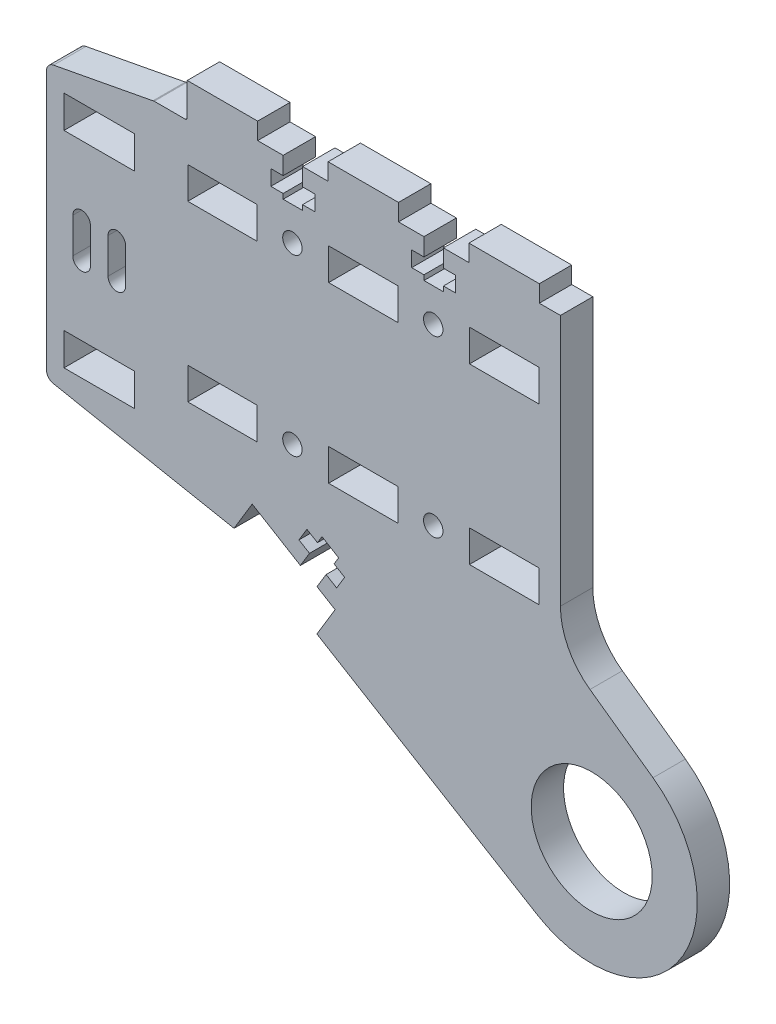
SolidWorks part; units mm, degrees
ref_plane "Front Plane" through (0, 0, 0) normal (0, 0, 1) x (1, 0, 0)
ref_plane "Top Plane" through (0, 0, 0) normal (0, 1, 0) x (1, 0, 0)
ref_plane "Right Plane" through (0, 0, 0) normal (1, 0, 0) x (0, 0, -1)
sketch "Sketch1" plane through (0, 0, 0) normal (0, 0, 1) x (1, 0, 0)
  line L0 (-38.0203, 0) -> (38.1796, 0) construction
  line L1 (31.7297, -12.8) -> (19.2297, -12.8)
  line L2 (38.1796, -12.8536) -> (38.1796, 12.8536)
  line L3 (31.7297, 12.8) -> (19.2297, 12.8)
  line L4 (-38.0203, -12.8) -> (-38.0203, 12.8)
  line L5 (38.1796, -12.8536) -> (-38.0203, 12.8) construction
  line L6 (38.1796, 12.8536) -> (-38.0203, -12.8) construction
  line L7 (6.3297, 18.542) -> (-6.1703, 18.542)
  line L8 (-19.0703, -18.542) -> (-31.5703, -12.8) construction
  line L9 (-19.0703, -12.8) -> (-31.5703, -18.542) construction
  line L10 (6.3297, -12.8) -> (-6.1703, -12.8)
  line L11 (-19.0703, -12.8) -> (-31.5703, -12.8)
  line L12 (31.7297, -12.8) -> (31.7297, -18.542)
  line L13 (19.2297, -12.8) -> (19.2297, -18.542)
  line L14 (38.1796, 28.575) -> (31.8297, 28.575)
  line L15 (-19.0703, 12.8) -> (-19.0703, 18.542)
  line L16 (-19.0703, 18.542) -> (-31.5703, 18.542)
  line L17 (-31.5703, 12.8) -> (-31.5703, 18.542)
  line L18 (-19.0703, 12.8) -> (-31.5703, 18.542) construction
  line L19 (-19.0703, 18.542) -> (-31.5703, 12.8) construction
  line L20 (-6.1703, 12.8) -> (-6.1703, 18.542)
  line L21 (6.3297, 12.8) -> (6.3297, 18.542)
  line L22 (31.7297, 18.542) -> (19.2297, 18.542)
  line L23 (19.2297, 12.8) -> (19.2297, 18.542)
  line L24 (31.7297, 12.8) -> (31.7297, 18.542)
  line L25 (-19.0703, 12.8) -> (-31.5703, 12.8)
  line L26 (6.3297, 12.8) -> (-6.1703, 12.8)
  line L27 (-38.0203, 12.8) -> (-38.0203, 28.575)
  line L28 (0.0797, 0) -> (0.0797, 28.575) construction
  line L29 (11.0271, 28.575) -> (6.4297, 28.575)
  line L30 (38.1796, 28.575) -> (38.1796, 12.8536)
  line L31 (31.7297, -18.542) -> (19.2297, -18.542)
  line L32 (6.3297, -12.8) -> (6.3297, -18.542)
  line L33 (-6.1703, -12.8) -> (-6.1703, -18.542)
  line L34 (-31.5703, -12.8) -> (-31.5703, -18.542)
  line L35 (-19.0703, -18.542) -> (-31.5703, -18.542)
  line L36 (-19.0703, -12.8) -> (-19.0703, -18.542)
  line L37 (6.3297, -18.542) -> (-6.1703, -18.542)
  line L38 (31.7297, -12.8) -> (19.2297, -12.8)
  line L39 (-19.0703, -12.8) -> (-31.5703, -12.8)
  line L40 (6.3297, -12.8) -> (-6.1703, -12.8)
  line L41 (6.3297, 12.8) -> (19.2297, 12.8) construction
  line L42 (-38.0203, -25.196) -> (31.432, -67.11)
  line L43 (38.1796, -25.196) -> (52.3348, -35.2893)
  line L44 (-10.8677, 22.1694) -> (-14.3729, 22.1694) construction
  line L45 (-8.6516, 24.0109) -> (-16.5891, 24.0109) construction
  line L46 (-10.8677, 26.9875) -> (-14.3729, 26.9875) construction
  line L47 (-12.6203, 28.575) -> (-12.6203, 24.5335) construction
  line L48 (-6.1703, 12.8) -> (-19.0703, 12.8) construction
  line L49 (-14.3729, 21.717) -> (-14.3729, 22.6219)
  line L50 (12.7797, 0) -> (12.7797, 28.575) construction
  line L51 (14.5323, 25.4) -> (16.7484, 25.4)
  line L52 (14.5323, 22.6219) -> (16.7484, 22.6219)
  line L53 (11.0271, 25.4) -> (11.0271, 28.575)
  line L54 (-10.8677, 21.717) -> (-10.8677, 22.6219)
  line L55 (-38.0203, -12.8) -> (-38.0203, -25.196)
  line L56 (14.5323, 25.4) -> (14.5323, 28.575)
  line L57 (12.7797, 28.575) -> (12.7797, 24.5335) construction
  line L58 (38.1796, -12.8536) -> (38.1796, -25.196)
  line L59 (11.0271, 26.9875) -> (14.5323, 26.9875) construction
  line L60 (8.8109, 22.6219) -> (11.0271, 22.6219)
  line L61 (8.8109, 22.6219) -> (8.8109, 25.4)
  line L62 (8.8109, 25.4) -> (11.0271, 25.4)
  line L63 (16.7484, 22.6219) -> (16.7484, 25.4)
  line L64 (12.7797, 24.5335) -> (12.7797, 20.1202) construction
  line L65 (8.8109, 24.0109) -> (16.7484, 24.0109) construction
  line L66 (11.0271, 21.717) -> (14.5323, 21.717)
  line L67 (11.0271, 21.717) -> (11.0271, 22.6219)
  line L68 (-6.2703, 28.575) -> (-10.8677, 28.575)
  line L69 (14.5323, 21.717) -> (14.5323, 22.6219)
  line L70 (12.7797, 20.1202) -> (12.7797, 21.717) construction
  line L71 (11.0271, 22.1694) -> (14.5323, 22.1694) construction
  line L72 (-10.8677, 21.717) -> (-14.3729, 21.717)
  line L73 (-16.5891, 22.6219) -> (-16.5891, 25.4)
  line L74 (-8.6516, 25.4) -> (-10.8677, 25.4)
  line L75 (-8.6516, 22.6219) -> (-8.6516, 25.4)
  line L76 (-8.6516, 22.6219) -> (-10.8677, 22.6219)
  line L77 (-14.3729, 25.4) -> (-14.3729, 28.575)
  line L78 (-10.8677, 25.4) -> (-10.8677, 28.575)
  line L79 (-14.3729, 22.6219) -> (-16.5891, 22.6219)
  line L80 (-14.3729, 25.4) -> (-16.5891, 25.4)
  line L81 (-14.3729, 28.575) -> (-18.9703, 28.575)
  line L82 (19.1297, 31.623) -> (19.1297, 28.575)
  line L83 (-6.2703, 31.623) -> (6.4297, 31.623)
  line L84 (-6.2703, 31.623) -> (-6.2703, 28.575)
  line L85 (31.8297, 31.623) -> (31.8297, 28.575)
  line L86 (6.4297, 31.623) -> (6.4297, 28.575)
  line L87 (0.0797, 28.575) -> (0.0797, 31.623) construction
  line L88 (-6.2703, 30.099) -> (6.4297, 30.099) construction
  line L89 (31.8297, 30.099) -> (19.1297, 30.099) construction
  line L90 (31.8297, 31.623) -> (19.1297, 31.623)
  line L91 (19.1297, 28.575) -> (14.5323, 28.575)
  line L92 (-18.9703, 31.623) -> (-18.9703, 28.575)
  line L93 (-31.6703, 31.623) -> (-18.9703, 31.623)
  line L94 (-31.6703, 30.099) -> (-18.9703, 30.099) construction
  line L95 (-31.6703, 31.623) -> (-31.6703, 28.575)
  line L96 (-31.6703, 28.575) -> (-38.0203, 28.575)
  arc A0 (31.432, -67.11) -> (52.3348, -35.2893) centre (41.275, -50.8) ccw
  circle A1 centre (12.7, 15.721) radius 1.7526
  circle A2 centre (-12.7, 15.721) radius 1.7526
  circle A3 centre (12.7, -15.721) radius 1.7526
  circle A4 centre (-12.7, -15.721) radius 1.7526
  circle A6 centre (41.275, -50.8) radius 10.9125
  point P0 (0, 0)
  point P8 (-25.3203, 15.671)
  point P16 (12.7, 30.1625)
  point P37 (-25.3203, -15.671)
  point P55 (12.7797, 26.9875)
  point P59 (12.7797, 24.0109)
  point P60 (-0.4211, 99.3522)
  point P62 (-25.6211, 23.1522)
  point P65 (12.7797, 22.1694)
  point P70 (-3.225, -28.575)
  point P73 (12.7797, 24.0109)
  point P91 (-12.6203, 24.0109)
  point P92 (-12.6203, 22.1694)
  point P97 (-12.6203, 26.9875)
  point P98 (-12.5407, 30.1625)
  point P99 (0.0797, 30.099)
  point P117 (25.4797, 30.099)
  point P120 (-25.3203, 30.099)
  dimension "D3" = 12.5
  dimension "D5" = 50.8
  dimension "D6" = 41.275
  dimension "D8" = 12.7
  dimension "D13" = 3.5052
  dimension "D11" = 28.575
  dimension "D19" = 21.825
  dimension "D7" = 38.1
  dimension "D1" = 25.6
  dimension "D2" = 76.2
  dimension "D4" = 5.742
  dimension "D9" = 12.7
  dimension "D10" = 3
  dimension "D12" = 2.921
  dimension "D14" = 2.921
  dimension "D15" = 15.721
  dimension "D16" = 12.7
  dimension "D17" = 3.048
  dimension "D20" = 9.525
  dimension "D21" = 9.525
  dimension "D18" = 12.7
  dimension "D22" = 3.5052
  dimension "D23" = 2.7781
  dimension "D24" = 7.9375
  dimension "D25" = 3.175
  dimension "D26" = 0.9049
extrude "Boss-Extrude1" add sketch "Sketch1" along normal blind 5.842 contours L58 L2 L30 L27 L4 L55 A4 L32 L37 L33 L10 L11 L36 L35 L34 L12 L31 L13 L1 L21 L26 L20 L7 L15 L25 L17 L16 L24 L3 L23 L22 region at (7.1681, -13.709, 0)
fillet "Fillet1" [suppressed] radius 3.175
fillet "Fillet2" [suppressed] radius 3.175
fillet "Fillet3" [suppressed] radius 3.175
sketch "Sketch3" [suppressed] plane through (0, 0, 5.842) normal (0, 0, 1) x (1, 0, 0)
  line L0 (12.6, 94.996) -> (12.7, -15.721) construction
  circle A0 centre (12.7147, -32.004) radius 2.413
  dimension "D1" = 4.826
  dimension "D2" = 127
extrude "Cut-Extrude2" [suppressed] cut sketch "Sketch3" against normal through all
sketch "Sketch5" [suppressed] plane through (0, 0, 5.842) normal (0, 0, 1) x (1, 0, 0)
  line L1 (-55.0734, 111.0269) -> (34.825, 111.0269)
  line L2 (-55.0734, 111.0269) -> (-55.0734, 25.146)
  line L3 (-55.0734, 25.146) -> (34.825, 25.146)
  line L4 (34.825, 111.0269) -> (34.825, 25.146)
extrude "Cut-Extrude3" [suppressed] cut sketch "Sketch5" against normal through all
sketch "Sketch6" [suppressed] plane through (0, 0, 5.842) normal (0, 0, 1) x (1, 0, 0)
  line L0 (-34.925, 25.146) -> (-33.9441, 25.146) construction
  line L1 (31.4879, 25.146) -> (-22.4871, 25.146)
  line L2 (31.4879, 78.486) -> (34.6629, 74.676)
  line L3 (31.4879, 78.486) -> (-20.5821, 78.486)
  line L4 (-22.4871, 25.146) -> (-25.0279, 25.146)
  line L5 (34.6629, 25.146) -> (-22.4871, 78.486) construction
  line L6 (34.6629, 78.486) -> (-22.4871, 25.146) construction
  line L7 (6.0879, 25.146) -> (6.0879, 48.411) construction
  line L8 (-31.75, 25.146) -> (-22.4871, 51.816)
  line L9 (-38.1, -25.146) -> (-38.1, 25.4) construction
  line L10 (34.6629, 74.676) -> (34.6629, 41.021)
  line L11 (-31.75, 25.146) -> (-25.0279, 25.146)
  line L12 (-22.4871, 51.816) -> (-22.4871, 71.3764)
  line L13 (31.4879, 70.866) -> (31.4879, 42.926) construction
  line L14 (31.4879, 37.846) -> (31.4879, 25.146)
  line L15 (31.4879, 37.846) -> (34.6629, 41.021)
  circle A0 centre (31.4879, 70.866) radius 1.651
  circle A1 centre (31.4879, 42.926) radius 1.651
  circle A2 centre (-20.5821, 74.676) radius 1.651
  circle A3 centre (-19.3121, 27.686) radius 1.651
  arc A4 (-20.5821, 78.486) -> (-22.4871, 71.3764) centre (-20.5821, 74.676) ccw
  point P0 (6.0879, 51.816)
  point P13 (-25.7515, 23.0626)
  point P14 (-16.4886, 49.7326)
  dimension "D5" = 3.302
  dimension "D6" = 3.302
  dimension "D9" = 12.7
  dimension "D10" = 3.302
  dimension "D12" = 3.302
  dimension "D1" = 53.34
  dimension "D2" = 57.15
  dimension "D3" = 6.35
  dimension "D7" = 49.53
  dimension "D8" = 27.94
  dimension "D11" = 52.07
  dimension "D13" = 50.8
  dimension "D14" = 15.24
  dimension "D4" = 7.62
extrude "Boss-Extrude3" [suppressed] add sketch "Sketch6" against normal up to surface (5.842 mm away) up to face at (52.1875, -50.8, 0)
fillet "Fillet6" [suppressed] radius 3.175
fillet "Fillet7" [suppressed] radius 1.5875
sketch "Sketch7" [suppressed] plane through (0, 0, 5.842) normal (0, 0, 1) x (1, 0, 0)
  line L0 (20.9561, 53.086) -> (-41.1495, 53.086) construction
  line L2 (5.0811, 78.486) -> (5.0811, 25.1147) construction
  line L3 (30.7443, 78.486) -> (-20.5821, 78.486) construction
  line L4 (5.0811, 65.786) -> (5.0811, 40.386) construction
  line L5 (8.2561, 65.786) -> (8.2561, 40.386)
  line L6 (1.9061, 65.786) -> (1.9061, 40.386)
  line L7 (17.7811, 65.786) -> (17.7811, 40.386) construction
  line L8 (20.9561, 65.786) -> (20.9561, 40.386)
  line L9 (14.6061, 65.786) -> (14.6061, 40.386)
  line L10 (-24.5007, 53.086) -> (20.9561, 53.086) construction
  line L11 (-7.6189, 65.786) -> (-7.6189, 40.386) construction
  line L12 (-10.7939, 65.786) -> (-10.7939, 40.386)
  line L13 (-4.4439, 65.786) -> (-4.4439, 40.386)
  arc A0 (8.2561, 65.786) -> (1.9061, 65.786) centre (5.0811, 65.786) ccw
  arc A1 (1.9061, 40.386) -> (8.2561, 40.386) centre (5.0811, 40.386) ccw
  arc A2 (20.9561, 65.786) -> (14.6061, 65.786) centre (17.7811, 65.786) ccw
  arc A3 (14.6061, 40.386) -> (20.9561, 40.386) centre (17.7811, 40.386) ccw
  arc A4 (-10.7939, 65.786) -> (-4.4439, 65.786) centre (-7.6189, 65.786) cw
  arc A5 (-4.4439, 40.386) -> (-10.7939, 40.386) centre (-7.6189, 40.386) cw
  point P10 (5.0811, 53.086)
  point P18 (17.7811, 53.086)
  point P26 (-7.6189, 53.086)
  dimension "D2" = 3.175
  dimension "D1" = 25.4
  dimension "D3" = 25.4
  dimension "D4" = 2
extrude "Cut-Extrude4" [suppressed] cut sketch "Sketch7" against normal through all
sketch "Sketch9" [suppressed] plane through (0, 0, 5.842) normal (0, 0, 1) x (1, 0, 0)
  line L0 (-38.1, -7.52) -> (38.1, -7.52) construction
  line L1 (-38.1, -25.146) -> (-38.1, 21.971) construction
  line L2 (38.1, 21.971) -> (38.1, -25.146) construction
  line L3 (-19.15, 12.8) -> (-31.65, 12.8) construction
  text T0 "SERGE" font "Roboto Condensed" height in points 42
  dimension "D1" = 20.32
extrude "Cut-Extrude5" [suppressed] cut sketch "Sketch9" against normal blind 0.3969
sketch "Sketch10" [suppressed] plane through (0, 0, 5.842) normal (0, 0, 1) x (1, 0, 0)
  line L0 (-38.1, -4.345) -> (38.1, -4.345) construction
  line L1 (-38.1, -25.146) -> (-38.1, 21.971) construction
  line L2 (38.1, 21.971) -> (38.1, -25.146) construction
  line L3 (-19.15, 12.8) -> (-31.65, 12.8) construction
  text T0 "SERGE" font "Bebas Neue" height in points 36
  dimension "D1" = 17.145
extrude "Cut-Extrude6" [suppressed] cut sketch "Sketch10" against normal blind 0.1984
sketch "Sketch11" [suppressed] plane through (0, 0, 5.842) normal (0, 0, 1) x (1, 0, 0)
  line L0 (12.6, 94.996) -> (12.7, 15.721) construction
  line L1 (9.467, 61.7085) -> (15.817, 61.7085) construction
  line L2 (9.467, 63.296) -> (15.817, 63.296)
  line L3 (9.467, 60.121) -> (15.817, 60.121)
  line L4 (31.75, 55.3585) -> (-6.45, 55.3585) construction
  line L5 (-6.45, 61.4095) -> (-6.45, 28.321) construction
  line L6 (9.4508, 74.4085) -> (15.8008, 74.4085) construction
  line L7 (9.4508, 75.996) -> (15.8008, 75.996)
  line L8 (9.4508, 72.821) -> (15.8008, 72.821)
  line L9 (9.4345, 87.1085) -> (15.7845, 87.1085) construction
  line L10 (9.4345, 88.696) -> (15.7845, 88.696)
  line L11 (9.4345, 85.521) -> (15.7845, 85.521)
  line L12 (9.4345, 23.6085) -> (15.7845, 23.6085) construction
  line L13 (9.4345, 22.021) -> (15.7845, 22.021)
  line L14 (9.4345, 25.196) -> (15.7845, 25.196)
  line L15 (9.4508, 36.3085) -> (15.8008, 36.3085) construction
  line L16 (9.4508, 34.721) -> (15.8008, 34.721)
  line L17 (9.4508, 37.896) -> (15.8008, 37.896)
  line L18 (9.467, 49.0085) -> (15.817, 49.0085) construction
  line L19 (9.467, 47.421) -> (15.817, 47.421)
  line L20 (9.467, 50.596) -> (15.817, 50.596)
  arc A0 (9.467, 63.296) -> (9.467, 60.121) centre (9.467, 61.7085) ccw
  arc A1 (15.817, 60.121) -> (15.817, 63.296) centre (15.817, 61.7085) ccw
  arc A2 (9.4508, 75.996) -> (9.4508, 72.821) centre (9.4508, 74.4085) ccw
  arc A3 (15.8008, 72.821) -> (15.8008, 75.996) centre (15.8008, 74.4085) ccw
  arc A4 (9.4345, 88.696) -> (9.4345, 85.521) centre (9.4345, 87.1085) ccw
  arc A5 (15.7845, 85.521) -> (15.7845, 88.696) centre (15.7845, 87.1085) ccw
  arc A6 (9.4345, 22.021) -> (9.4345, 25.196) centre (9.4345, 23.6085) cw
  arc A7 (15.7845, 25.196) -> (15.7845, 22.021) centre (15.7845, 23.6085) cw
  arc A8 (9.4508, 34.721) -> (9.4508, 37.896) centre (9.4508, 36.3085) cw
  arc A9 (15.8008, 37.896) -> (15.8008, 34.721) centre (15.8008, 36.3085) cw
  arc A10 (9.467, 47.421) -> (9.467, 50.596) centre (9.467, 49.0085) cw
  arc A11 (15.817, 50.596) -> (15.817, 47.421) centre (15.817, 49.0085) cw
  point P6 (12.642, 61.7085)
  point P16 (12.65, 55.3585)
  point P19 (12.6258, 74.4085)
  point P26 (12.6095, 87.1085)
  point P32 (12.6095, 23.6085)
  point P39 (12.6258, 36.3085)
  point P46 (12.642, 49.0085)
  dimension "D1" = 1.5875
  dimension "D2" = 6.35
  dimension "D3" = 6.35
  dimension "D4" = 3
extrude "Cut-Extrude7" [suppressed] cut sketch "Sketch11" against normal through all
fillet "Fillet8" [suppressed] radius 25.4
fillet "Fillet10" [suppressed] radius 12.7
fillet "Fillet11" radius 12.7 1 edges at (38.1796, -25.196, 2.921)
sketch "Sketch12" [suppressed] plane through (0, 0, 5.842) normal (0, 0, 1) x (1, 0, 0)
  line L1 (-59.2155, 110.7085) -> (34.825, 110.7085)
  line L2 (-59.2155, 110.7085) -> (-59.2155, 25.146)
  line L3 (-59.2155, 25.146) -> (34.825, 25.146)
  line L4 (34.825, 110.7085) -> (34.825, 25.146)
  line L5 (-59.2155, 110.7085) -> (34.825, 25.146) construction
  line L6 (-59.2155, 25.146) -> (34.825, 110.7085) construction
  arc A0 (31.65, 28.321) -> (34.825, 25.146) centre (34.825, 28.321) ccw construction
  point P4 (-12.1952, 67.9272)
sketch "Sketch16" plane through (0, 0, 0) normal (0, 0, -1) x (-1, 0, 0)
  line L0 (-35.6396, 28.575) -> (-35.6396, -23.3849)
  line L1 (-38.1796, 28.575) -> (-31.8297, 28.575) construction
  line L2 (-35.6396, -23.3849) -> (-43.5064, -28.9942)
  line L3 (-43.5064, -28.9942) -> (-52.3348, -35.2893) construction
  line L4 (-38.1796, 28.575) -> (-38.1796, -18.6537) construction
  line L5 (-38.1796, 28.575) -> (-35.6396, 28.575)
  line L6 (-38.1796, 28.575) -> (-38.1796, -18.6537)
  arc A0 (-43.5064, -28.9942) -> (-38.1796, -18.6537) centre (-50.8796, -18.6537) ccw construction
  arc A1 (-43.5064, -28.9942) -> (-38.1796, -18.6537) centre (-50.8796, -18.6537) ccw
  dimension "D1" = 2.54
extrude "Cut-Extrude9" cut sketch "Sketch16" against normal through all
fillet "Fillet12" radius 12.7 1 edges at (35.6396, -23.3849, 2.921)
sketch "Sketch17" plane through (0, 0, 5.842) normal (0, 0, 1) x (1, 0, 0)
  line L0 (-31.6703, 28.575) -> (-38.0203, 28.575) construction
  line L1 (-31.6703, 28.575) -> (-38.0203, 28.575)
  line L2 (-31.6703, 28.575) -> (-31.6703, 25.4)
  line L3 (-31.6703, 25.4) -> (-38.0203, 25.4)
  line L4 (-38.0203, 28.575) -> (-38.0203, 25.4)
  line L5 (-38.0203, -25.196) -> (-38.0203, 28.575) construction
  dimension "D1" = 3.175
extrude "Cut-Extrude10" cut sketch "Sketch17" against normal through all
fillet "Fillet13" radius 0.4 2 edges at (-38.0203, 25.4, 2.921) (-31.6703, 25.4, 2.921)
sketch "Sketch18" plane through (0, 0, 5.842) normal (0, 0, 1) x (1, 0, 0)
  line L0 (-23.2347, -34.1191) -> (-8.2838, -43.1418)
  line L1 (-23.2347, -34.1191) -> (-19.9537, -28.6824)
  line L2 (-8.2838, -43.1418) -> (-5.0028, -37.7051)
  line L3 (-19.9537, -28.6824) -> (-11.2604, -33.9287)
  line L4 (-38.0203, -25.196) -> (31.432, -67.11) construction
  line L5 (-31.5703, -12.8) -> (-31.5703, -18.542) construction
  line L6 (-6.6433, -40.4235) -> (-21.5942, -31.4007) construction
  line L8 (-9.7599, -34.8343) -> (-1.8729, -21.7654) construction
  line L9 (-9.6199, -31.2104) -> (-11.2604, -33.9287)
  line L10 (-8.2594, -35.7398) -> (-5.0028, -37.7051)
  line L12 (-6.6189, -33.0215) -> (-8.2594, -35.7398)
  line L13 (-9.6199, -31.2104) -> (-8.2594, -35.7398) construction
  line L14 (-11.2604, -33.9287) -> (-6.6189, -33.0215) construction
  line L15 (-11.5173, -30.0653) -> (-9.6199, -31.2104)
  line L16 (-11.5173, -30.0653) -> (-10.0819, -27.6867)
  line L17 (-4.7215, -34.1665) -> (-3.286, -31.788)
  line L18 (-10.0819, -27.6867) -> (-8.1845, -28.8318)
  line L19 (-11.5173, -30.0653) -> (-3.286, -31.788) construction
  line L20 (-4.7215, -34.1665) -> (-10.0819, -27.6867) construction
  line L21 (-7.3642, -27.4726) -> (-8.1845, -28.8318)
  line L22 (-7.3642, -27.4726) -> (-4.3632, -29.2838)
  line L23 (-6.6189, -33.0215) -> (-4.7215, -34.1665)
  line L24 (-4.3632, -29.2838) -> (-5.1834, -30.6429)
  line L25 (-7.3642, -27.4726) -> (-5.1834, -30.6429) construction
  line L26 (-8.1845, -28.8318) -> (-4.3632, -29.2838) construction
  line L27 (-5.1834, -30.6429) -> (-3.286, -31.788)
  point P7 (-31.5703, -15.671)
  point P15 (-8.9396, -33.4751)
  point P16 (-7.4017, -30.9266)
  point P21 (-6.2738, -29.0578)
  point P32 (-14.1187, -35.9121)
  dimension "D1" = 17.4625
  dimension "D2" = 6.35
  dimension "D3" = 28.575
  dimension "D4" = 3.5052
  dimension "D5" = 3.175
  dimension "D6" = 7.9375
  dimension "D7" = 2.7781
  dimension "D8" = 3.5052
  dimension "D9" = 1.5875
  dimension "D10" = 3.175
extrude "Cut-Extrude11" cut sketch "Sketch18" against normal through all
sketch "Sketch20" plane through (0, 0, 0) normal (0, 0, -1) x (-1, 0, 0)
  line L0 (19.0703, -18.542) -> (31.5703, -18.542) construction
  line L1 (53.8953, -24.384) -> (41.1953, -24.384)
  line L2 (53.8953, -24.384) -> (53.8953, -18.542)
  line L3 (53.8953, -18.542) -> (41.1953, -18.542)
  line L4 (41.1953, -24.384) -> (41.1953, -18.542)
  line L5 (47.5453, -18.542) -> (47.5453, -24.384) construction
  line L6 (53.8953, -21.463) -> (41.1953, -21.463) construction
  line L7 (38.0203, -25.196) -> (38.0203, 25) construction
  line L8 (19.0703, 18.542) -> (31.5703, 18.542) construction
  line L9 (53.8953, 12.7) -> (41.1953, 12.7)
  line L10 (53.8953, 12.7) -> (53.8953, 18.542)
  line L11 (53.8953, 18.542) -> (41.1953, 18.542)
  line L12 (41.1953, 12.7) -> (41.1953, 18.542)
  line L13 (47.5453, 18.542) -> (47.5453, 12.7) construction
  line L14 (53.8953, 15.621) -> (41.1953, 15.621) construction
  line L15 (47.5453, -21.463) -> (47.5453, 15.621) construction
  line L16 (44.3703, 0.254) -> (44.3703, -6.096) construction
  line L17 (45.9578, 0.254) -> (45.9578, -6.096)
  line L18 (42.7828, 0.254) -> (42.7828, -6.096)
  line L19 (47.5453, -2.921) -> (-35.6396, -2.921) construction
  line L20 (-35.6396, -16.8426) -> (-35.6396, 28.575) construction
  line L21 (50.7203, 0.254) -> (50.7203, -6.096) construction
  line L22 (49.1328, 0.254) -> (49.1328, -6.096)
  line L23 (52.3078, 0.254) -> (52.3078, -6.096)
  line L24 (37.6203, 25.4) -> (57.0703, 21.717)
  line L25 (23.2347, -34.1191) -> (57.0703, -27.559)
  line L27 (57.0703, -27.559) -> (57.0703, 21.717)
  line L28 (38.0203, -25.196) -> (23.2347, -34.1191) construction
  line L29 (38.0203, -25.196) -> (38.0203, 25)
  line L30 (38.0203, -25.196) -> (23.2347, -34.1191)
  arc A0 (45.9578, 0.254) -> (42.7828, 0.254) centre (44.3703, 0.254) ccw
  arc A1 (42.7828, -6.096) -> (45.9578, -6.096) centre (44.3703, -6.096) ccw
  arc A2 (49.1328, 0.254) -> (52.3078, 0.254) centre (50.7203, 0.254) cw
  arc A3 (52.3078, -6.096) -> (49.1328, -6.096) centre (50.7203, -6.096) cw
  arc A4 (38.0203, 25) -> (37.6203, 25.4) centre (37.6203, 25) ccw construction
  arc A5 (38.0203, 25) -> (37.6203, 25.4) centre (37.6203, 25) ccw
  point P0 (47.5453, -21.463)
  point P11 (47.5453, 15.621)
  point P26 (44.3703, -2.921)
  point P39 (50.7203, -2.921)
  dimension "D6" = 1.5875
  dimension "D1" = 12.7
  dimension "D2" = 5.842
  dimension "D3" = 9.525
  dimension "D4" = 12.7
  dimension "D5" = 5.842
  dimension "D7" = 6.35
  dimension "D8" = 3.175
  dimension "D9" = 19.05
  dimension "D10" = 3.175
  dimension "D11" = 3.175
extrude "Boss-Extrude5" add sketch "Sketch20" against normal up to surface (5.842 mm away) contours A5 L29 L30 L25 L27 L24 A1 L18 A0 L17 L1 L4 L3 L2 L9 L12 L11 L10 L23 A3 L22 A2 region at (-46.5222, -4.3854, 0) up to face at (-1.307, 5.7101, 5.842)
fillet "Fillet17" radius 1.5875 3 edges at (-37.7666, 25.3723, 2.921) (-57.0703, -27.559, 2.921) (-57.0703, 21.717, 2.921)
sketch "Sketch19" [suppressed] plane through (0, 0, 0) normal (0, 0, -1) x (-1, 0, 0)
  line L0 (31.5703, -18.542) -> (50.7203, -18.542) construction
  line L1 (38.0203, -18.0269) -> (38.0203, 25) construction
  line L2 (38.0203, -18.0269) -> (38.0203, -15.113)
  line L3 (38.0203, 3.4866) -> (50.7203, -15.113)
  line L4 (31.8823, -28.9002) -> (50.7203, -27.813)
  line L5 (50.7203, -27.813) -> (50.7203, -15.113)
  line L6 (50.7203, -21.463) -> (37.5467, -21.463) construction
  line L7 (38.0203, -15.113) -> (38.0203, -7.7744)
  line L8 (38.0203, -24.384) -> (47.5453, -24.384)
  line L9 (38.0203, -24.384) -> (38.0203, -18.542)
  line L10 (38.0203, -18.542) -> (47.5453, -18.542)
  line L11 (47.5453, -24.384) -> (47.5453, -18.542)
  line L12 (42.7828, -18.542) -> (42.7828, -24.384) construction
  line L13 (38.0203, -21.463) -> (47.5453, -21.463) construction
  line L15 (38.0203, -7.7744) -> (38.0203, 3.4866)
  arc A0 (31.8823, -28.9002) -> (38.0203, -18.0269) centre (25.3203, -18.0269) ccw construction
  arc A1 (31.8823, -28.9002) -> (38.0203, -18.0269) centre (25.3203, -18.0269) ccw
  point P12 (42.7828, -21.463)
  dimension "D1" = 12.7
  dimension "D2" = 12.7
  dimension "D3" = 9.525
  dimension "D4" = 5.842
  dimension "D5" = 7.9375
extrude "Boss-Extrude4" [suppressed] add sketch "Sketch19" against normal up to surface (5.842 mm away) up to face at (-4.6993, 5.9613, 5.842)
fillet "Fillet14" [suppressed] radius 25.4
fillet "Fillet15" [suppressed] radius 1.5875
